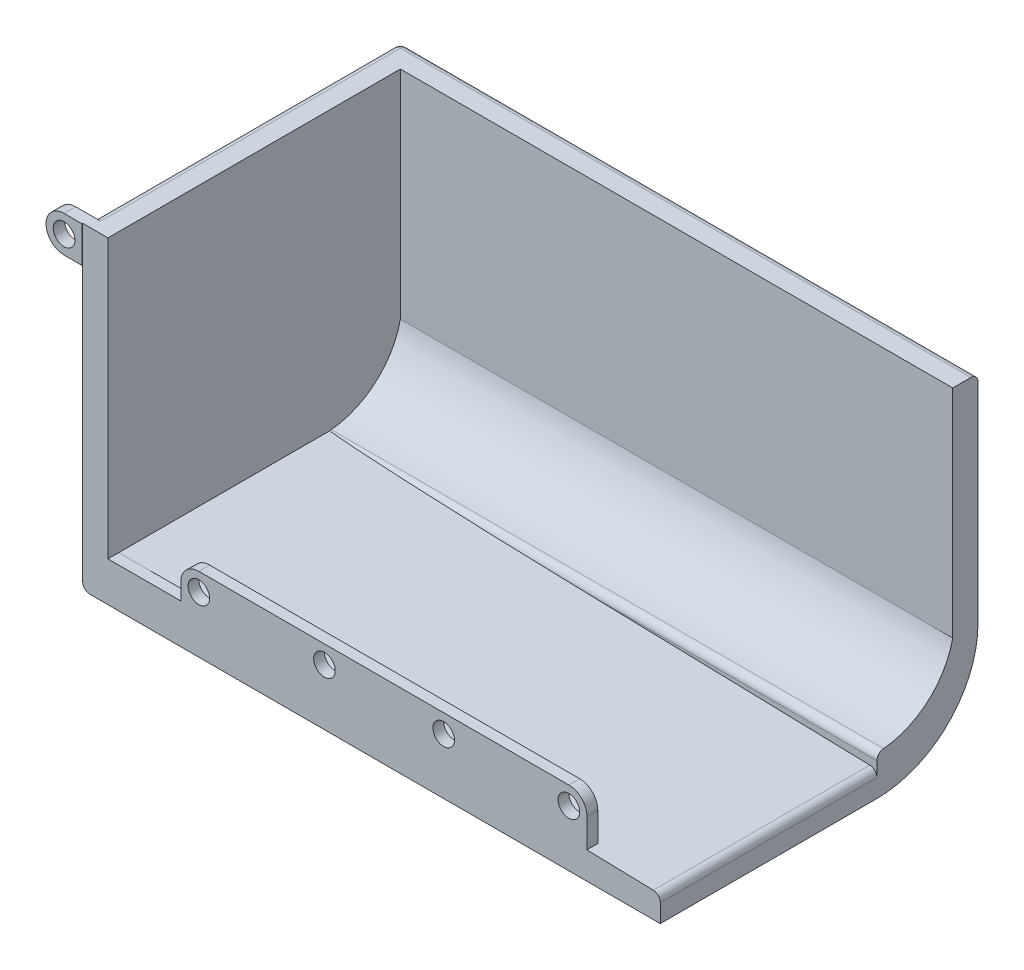
SolidWorks part; units mm, degrees
ref_plane "Front Plane" through (0, 0, 0) normal (0, 0, 1) x (1, 0, 0)
ref_plane "Top Plane" through (0, 0, 0) normal (0, 1, 0) x (1, 0, 0)
ref_plane "Right Plane" through (0, 0, 0) normal (1, 0, 0) x (0, 0, -1)
sketch "Sketch1" plane through (0, 0, 0) normal (1, 0, 0) x (0, 0, -1)
  line L3 (25.4, 0) -> (25.4, -10.16)
  line L4 (25.4, -10.16) -> (101.6, -10.16)
  line L5 (137.16, 25.4) -> (137.16, 101.6)
  line L7 (127, 101.6) -> (137.16, 101.6)
  line L8 (25.4, 0) -> (25.4, 101.6)
  line L11 (25.4, 101.6) -> (127, 101.6)
  arc A1 (137.16, 25.4) -> (101.6, -10.16) centre (101.6, 25.4) cw
extrude "Boss-Extrude1" add sketch "Sketch1" along normal blind 203.2
sketch "Sketch4" plane through (203.2, 0, 0) normal (1, 0, 0) x (0, 0, -1)
  line L0 (101.6, 3.81) -> (25.4, 3.81)
  line L1 (101.6, 3.81) -> (25.4, 3.81)
  line L2 (25.4, 3.81) -> (25.4, -1.27)
  line L4 (128.27, 25.4) -> (128.27, 101.6)
  line L5 (128.27, 25.4) -> (128.27, 101.6)
  line L6 (25.4, 101.6) -> (25.4, -10.16) construction
  line L7 (25.4, -1.27) -> (25.4, -10.16)
  line L8 (25.4, -10.16) -> (101.6, -10.16)
  line L9 (128.27, 101.6) -> (137.16, 101.6)
  line L10 (137.16, 101.6) -> (137.16, 25.4)
  line L11 (25.4, 101.6) -> (128.27, 101.6)
  line L12 (25.4, 101.6) -> (25.4, -1.27)
  line L14 (123.19, 25.4) -> (123.19, 101.6) construction
  line L15 (101.6, -1.27) -> (25.4, -1.27) construction
  arc A0 (101.6, 3.81) -> (128.27, 25.4) centre (101.6, 31.0776) ccw
  arc A2 (101.6, -10.16) -> (137.16, 25.4) centre (101.6, 25.4) ccw
  arc A3 (101.6, -1.27) -> (128.27, 25.4) centre (101.6, 25.4) ccw
  arc A5 (101.6, 3.81) -> (123.19, 25.4) centre (101.6, 25.4) ccw construction
  arc A7 (101.6, -1.27) -> (128.27, 25.4) centre (101.6, 25.4) ccw construction
  line M3 (137.16, 101.6) -> (25.4, 101.6)
  line M4 (25.4, 101.6) -> (25.4, -10.16)
  dimension "D1" = 8.89
  dimension "D2" = 5.08
extrude "Cut-Extrude1" cut sketch "Sketch4" against normal blind 194.31 contours L0 A0 L5 M3 M4 region at (203.2, 53.3414, -76.1688)
sketch "Sketch5" plane through (0, 0, -25.4) normal (0, 0, 1) x (1, 0, 0)
  line L0 (8.89, 3.81) -> (8.89, -1.27)
  line L1 (8.89, -1.27) -> (203.2, -1.27)
  line L2 (203.2, 3.81) -> (203.2, -10.16) construction
  line L5 (8.89, 3.81) -> (203.2, -1.27)
  line L6 (8.89, 3.81) -> (203.2, 3.81)
  line L7 (203.2, 3.81) -> (203.2, -1.27)
  line L8 (8.89, 3.81) -> (203.2, 3.81)
  line L9 (203.2, -1.27) -> (203.2, 3.81)
  line M6 (203.2, 3.81) -> (8.89, 3.81)
  line M11 (203.2, -10.16) -> (203.2, 3.81)
extrude "Cut-Extrude2" cut sketch "Sketch5" against normal blind 76.2 contours L5 M6 M11 region at (138.43, 2.1167, -25.4)
fillet "Fillet1" radius 2.54 1 edges at (106.045, 3.81, -101.6)
sketch "Sketch8" plane through (0, 0, -25.4) normal (0, 0, 1) x (1, 0, 0)
  line L0 (8.89, 3.81) -> (203.2, -1.27)
  line L1 (203.2, -1.27) -> (203.2, 3.9092)
  line L2 (203.2, 3.9092) -> (8.89, 3.81)
  line L3 (112.3937, 3.8628) -> (145.4137, 3.8797)
  line L4 (106.045, 3.8596) -> (8.89, 3.81)
  line L7 (8.89, 3.81) -> (40.64, 3.8262)
  line L8 (99.6937, 3.8563) -> (112.3937, 3.8628)
  line L9 (177.3889, 3.896) -> (177.3889, 1.3784)
  line L10 (40.64, 3.8262) -> (85.0553, 3.8489)
  line L11 (203.2, 1.3784) -> (101.898, 1.3784) construction
  line L12 (203.2, 3.9092) -> (171.45, 3.893)
  line L13 (177.3889, 1.3784) -> (177.3889, -0.5952)
  line L14 (171.45, 3.893) -> (127, 3.8703)
  line L19 (177.3889, 9.6459) -> (177.3889, 3.896)
  line L22 (34.5189, 9.6459) -> (34.5189, 3.2927)
  line L24 (40.8689, 15.9959) -> (171.0389, 15.9959)
  arc A0 (106.045, 3.8596) -> (106.0489, 3.8596) centre (106.0431, 11.4796) ccw
  arc A2 (106.045, 3.8596) -> (106.0489, 3.8596) centre (106.0437, 10.2096) ccw
  circle A5 centre (127.002, 9.4966) radius 3.7935
  arc A6 (177.3889, 9.6459) -> (171.0389, 15.9959) centre (171.0389, 9.6459) ccw
  circle A7 centre (171.0389, 9.6459) radius 3.7935
  circle A9 centre (85.055, 9.6459) radius 3.7935
  arc A10 (40.8689, 15.9959) -> (34.5189, 9.6459) centre (40.8689, 9.6459) ccw
  circle A11 centre (40.8689, 9.6459) radius 3.7935
extrude "Boss-Extrude2" add sketch "Sketch8" against normal blind 3.81 contours L13 L9 L2 L3 L8 L4 L7 L0 | L24 A10 L22 L4 L2 L8 L3 L19 A6 A11 A5 A7 A9 region at (121.2226, 2.3703, -25.4) region at (105.8687, 9.9129, -25.4)
sketch "Sketch9" plane through (0, 0, -25.4) normal (0, 0, 1) x (1, 0, 0)
  line L0 (0, 101.6) -> (0, 88.9)
  line L1 (0, 101.6) -> (0, -10.16) construction
  line L2 (0, 88.9) -> (0, 86.9272)
  line L3 (-6.2959, 88.9) -> (0, 88.9)
  line L4 (-6.2959, 101.6) -> (0, 101.6)
  arc A0 (-6.2959, 101.6) -> (-6.2959, 88.9) centre (-6.2959, 95.25) ccw
  arc A1 (0, 94.4229) -> (0, 96.0771) centre (-6.2959, 95.25) ccw
  circle A2 centre (-6.2959, 95.25) radius 3.8155
  line M16 (0, 101.6) -> (0, -10.16)
extrude "Boss-Extrude3" add sketch "Sketch9" against normal blind 3.81 and the other way blind 0.254 contours L4 A0 L3 L0 A2 M16 region at (-0.1792, 98.8385, -25.4)
fillet "Fillet2" radius 2.54 1 edges at (101.6, 101.6, -137.16)
fillet "Fillet4" radius 2.54 1 edges at (203.2, -1.27, -63.5)
fillet "Fillet5" radius 2.54 5 edges at (0, -10.16, -63.5) (0, 101.6, -81.915) (0, 100.8561, -136.4161) (0, 0.2553, -126.7447) (0, 62.23, -137.16)
